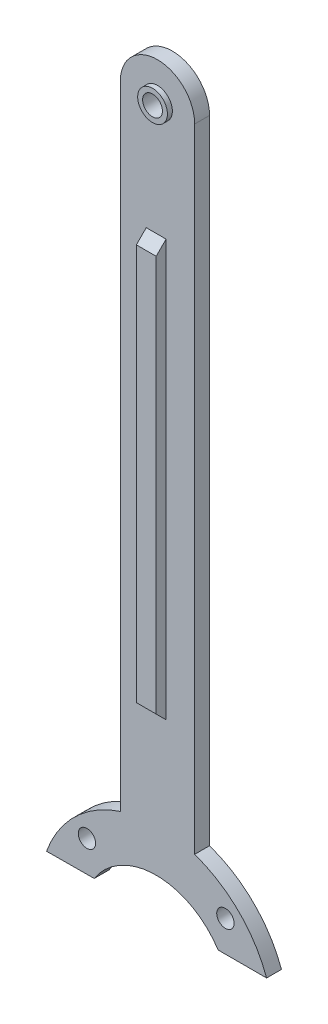
SolidWorks part; units mm, degrees
ref_plane "Front Plane" through (0, 0, 0) normal (0, 0, 1) x (1, 0, 0)
ref_plane "Top Plane" through (0, 0, 0) normal (0, 1, 0) x (1, 0, 0)
ref_plane "Right Plane" through (0, 0, 0) normal (1, 0, 0) x (0, 0, -1)
sketch "Sketch1" plane through (0, 0, 0) normal (0, 0, 1) x (1, 0, 0)
  line L0 (-51.1241, 36.9636) -> (-41.4972, 37.0214)
  line L1 (-16.5028, 37.0214) -> (-6.7154, 37.0214)
  line L4 (-21.232, 178.9998) -> (-21.232, 51.3742)
  line L5 (-36.232, 51.374) -> (-36.232, 178.9998)
  circle A0 centre (-42.9681, 43.289) radius 1.75
  circle A1 centre (-15.03, 43.289) radius 1.75
  arc A2 (-41.4972, 37.0214) -> (-16.5028, 37.0214) centre (-29, 29) cw
  arc A4 (-6.7154, 37.0214) -> (-21.232, 51.3742) centre (-29, 29) ccw
  arc A5 (-36.232, 51.374) -> (-51.1241, 36.9636) centre (-29, 29) ccw
  arc A6 (-21.232, 178.9998) -> (-36.232, 178.9998) centre (-28.732, 178.9998) ccw
  circle A7 centre (-28.732, 178.9998) radius 2
  dimension "D2" = 4
  dimension "D3" = 7.5
  dimension "D4" = 3.5
  dimension "D5" = 23.6843
  dimension "D6" = 23.5137
  dimension "D1" = 150
  dimension "D7" = 6.7154
  dimension "D8" = 15.03
  dimension "D9" = 21.232
  dimension "D10" = 43.289
  dimension "D14" = 42.9681
  dimension "D15" = 51.1241
extrude "Boss-Extrude1" add sketch "Sketch1" along normal blind 3
sketch "Sketch4" plane through (0, 0, 3) normal (0, 0, 1) x (1, 0, 0)
  circle A0 centre (-28.732, 178.9998) radius 2
  circle A2 centre (-28.732, 178.9998) radius 3
  dimension "D1" = 1
extrude "Boss-Extrude4" add sketch "Sketch4" along normal blind 1
sketch "Sketch5" plane through (0, 0, 3) normal (0, 0, 1) x (1, 0, 0)
  line L0 (-29, 64.0022) -> (-29, 164.0022)
  arc A0 (-21.232, 178.9998) -> (-36.232, 178.9998) centre (-28.732, 178.9998) ccw construction
  dimension "D1" = 100
  dimension "D2" = 15
extrude "Extrude-Thin1" add sketch "Sketch5" along normal blind 2 thin thin type two direction wall 2 second wall 2
chamfer "Chamfer1" distance 10 angle 45 2 edges at (-29, 164.0022, 5) (-29, 64.0022, 5)
